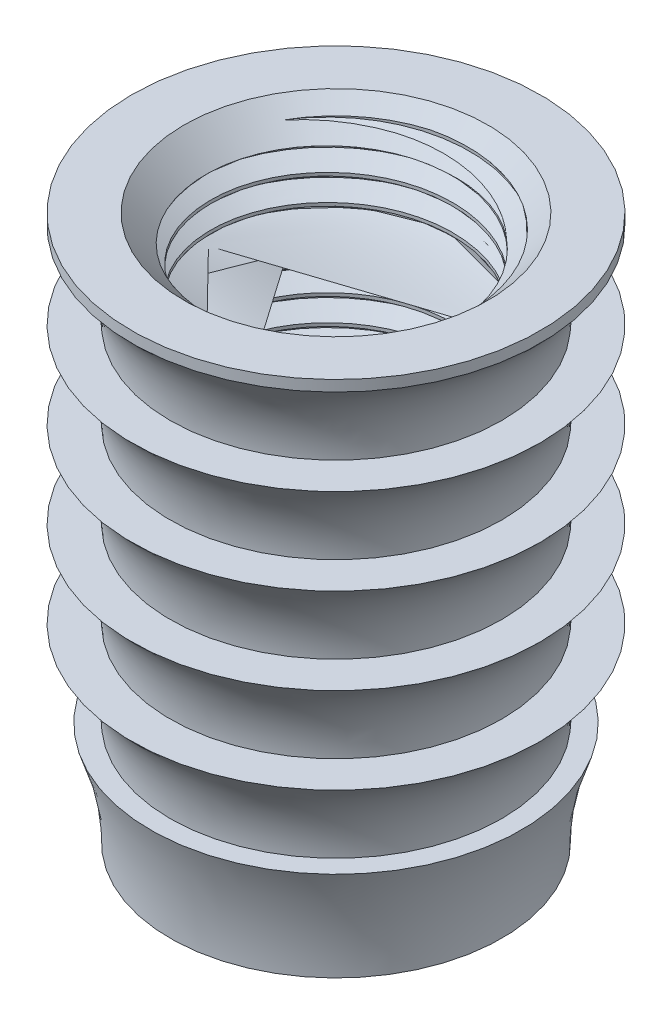
SolidWorks part; units mm, degrees
ref_plane "Front Plane" through (0, 0, 0) normal (0, 0, 1) x (1, 0, 0)
ref_plane "Top Plane" through (0, 0, 0) normal (0, 1, 0) x (1, 0, 0)
ref_plane "Right Plane" through (0, 0, 0) normal (1, 0, 0) x (0, 0, -1)
sketch "Sketch1" plane through (0, 0, 0) normal (0, 0, 1) x (1, 0, 0)
  line L0 (0, -4.7625) -> (0, 4.7625) construction
  line L1 (2.413, 0) -> (-2.413, 0) construction
  line L2 (2.413, 0) -> (2.413, -0.7938) construction
  line L3 (-3.5687, 4.7625) -> (3.5687, 4.7625) construction
  line L4 (-2.8956, -4.7625) -> (2.8956, -4.7625) construction
  line L5 (-3.2385, -0.7938) -> (3.2385, -0.7938) construction
  line L6 (3.5687, 4.7625) -> (155.9687, 4.7625) construction
  line L7 (-3.5687, 4.7625) -> (-8.3947, 4.7625) construction
  point P4 (0, 0)
  point P8 (0, 0)
  point P12 (0, 4.7625)
  point P15 (0, -4.7625)
  point P18 (0, -0.7938)
  dimension "Thread Size" = 4.826
  dimension "Thread Pitch" = 0.7937
  dimension "Installed Length" = 9.525
  dimension "OD" = 7.1374
  dimension "Small Dia" = 5.7912
  dimension "Barb Dia" = 6.477
  dimension "No of Barbs" = 152.4
  dimension "Botom Barb Proportion" = 4.826
sketch "Sketch2" plane through (0, 0, 0) normal (0, 0, 1) x (1, 0, 0)
  line L0 (-3.5687, 4.7625) -> (-3.5687, 4.572)
  line L3 (-2.8956, 3.0671) -> (-2.8956, 4.572) construction
  line L5 (-2.8956, 3.0671) -> (-2.8956, -2.9527)
  line L6 (-2.8956, -2.9527) -> (-3.2385, -2.9527)
  line L7 (-2.8956, -4.7625) -> (2.8956, -4.7625) construction
  line L8 (-3.5687, 4.7625) -> (-2.6543, 4.7625)
  line L9 (-3.5687, 4.7625) -> (3.5687, 4.7625) construction
  line L10 (-2.6543, 4.7625) -> (-2.413, 4.5212)
  line L11 (-2.413, 4.5212) -> (-2.413, -4.5212)
  line L12 (-2.413, -4.5212) -> (-2.6543, -4.7625)
  line L13 (-2.6543, -4.7625) -> (-2.8956, -4.7625)
  line L14 (-2.6543, 4.7625) -> (-2.413, 4.7625) construction
  line L15 (-2.413, 4.7625) -> (-2.413, 4.5212) construction
  line L16 (-2.6543, -4.7625) -> (-2.413, -4.7625) construction
  line L17 (-2.413, -4.7625) -> (-2.413, -4.5212) construction
  line L18 (0, 4.7625) -> (0, -4.7625) construction
  arc A0 (-3.5687, 4.572) -> (-2.8956, 3.0671) centre (-4.9146, 3.0671) cw
  arc A3 (-3.2385, -2.9527) -> (-2.8956, -4.7625) centre (-7.8428, -4.7625) cw
  dimension "D1" = 0.1905
  dimension "D2" = 1.8098
  dimension "D3" = 5.3086
  dimension "D4" = 1.5049
revolve "Revolve1" add sketch "Sketch2" angle 360 about L18
sketch "Sketch10" plane through (0, 0, 0) normal (0, 0, 1) x (1, 0, 0)
  line L1 (-2.8956, 3.0671) -> (-2.8956, 1.5621)
  line L2 (-2.8956, 3.0671) -> (-2.8956, -2.9527) construction
  line L3 (-2.8956, 3.0671) -> (-3.5687, 3.0671)
  line L4 (-2.8956, 3.0671) -> (-2.8956, 4.572) construction
  arc A0 (-3.5687, 3.0671) -> (-2.8956, 1.5621) centre (-4.9146, 1.5621) cw
revolve "Revolve5" add sketch "Sketch10" angle 360 about L0
pattern_linear "LPattern1" count 4 spacing 1.5049 along (0, -1, 0) of "Revolve5"
sketch "Sketch8" plane through (0, 0, 0) normal (0, 1, 0) x (1, 0, 0)
  line L0 (0, 0) -> (0, -2.413) construction
  circle A0 centre (0, 0) radius 2.413 construction
  point P0 (0, -2.413)
sketch "Sketch3" plane through (0, 0, 0) normal (0, 0, 1) x (1, 0, 0)
  line L1 (-2.413, -4.7625) -> (0, -4.7625)
  line L2 (-2.413, -4.7625) -> (-2.413, 4.7625)
  line L3 (-2.413, 4.7625) -> (0, 4.7625)
  line L4 (0, -4.7625) -> (0, 4.7625)
revolve "Revolve2" add sketch "Sketch3" angle 360 about L4
sketch "Sketch4" plane through (0, -4.7625, 0) normal (0, -1, 0) x (1, 0, 0)
  circle A1 centre (0, 0) radius 2.413
  circle A2 centre (0, 0) radius 2.413
  dimension "D1" = 0
curve "Helix/Spiral1" pitch 0.4547 height 10.3187 turns 22.6955
sketch "Sketch5" plane through (0, 0, 0) normal (0, 0, 1) x (1, 0, 0)
  line L0 (2.4614, -4.7346) -> (2.4614, -5.1892) construction
  line L1 (2.4614, -5.1892) -> (2.0676, -4.9619) construction
  line L2 (2.0676, -4.9619) -> (2.4614, -4.7346) construction
  line L3 (2.116, -4.9339) -> (2.116, -4.9898) construction
  line L4 (2.413, -4.7625) -> (2.413, -5.1613) construction
  line L5 (2.413, -4.9619) -> (2.4614, -4.9619) construction
  line L6 (2.0676, -4.9619) -> (2.116, -4.9619) construction
  line L7 (2.4372, -4.9619) -> (2.4372, -5.1753) construction
  line L8 (2.4614, -4.7346) -> (2.4372, -5.1753)
  line L9 (2.4372, -5.1753) -> (2.116, -4.9898)
  line L10 (2.116, -4.9898) -> (2.116, -4.9339)
  line L11 (2.116, -4.9339) -> (2.4614, -4.7346)
  line L12 (-2.8956, -4.7625) -> (2.8956, -4.7625) construction
  dimension "D1" = 0.4547
  dimension "D2" = 0.0559
sweep "Cut-Sweep1" cut profiles "Sketch5" path "Helix/Spiral1" align with end faces yes
sketch "Sketch6" plane through (0, 0, 0) normal (0, 0, 1) x (1, 0, 0)
  line L0 (-2.6543, -4.7625) -> (0, -2.1082)
  line L1 (0, -2.1082) -> (0, -4.7625)
  line L2 (-2.8956, -4.7625) -> (2.8956, -4.7625) construction
  line L3 (0, -4.7625) -> (-2.6543, -4.7625)
  line L4 (-2.413, -4.5212) -> (-2.6543, -4.7625) construction
  line L5 (-2.6543, 4.7625) -> (0, 4.7625) construction
  line L6 (0, 4.7625) -> (0, 2.1082) construction
  line L7 (0, 2.1082) -> (-2.6543, 4.7625) construction
  line L8 (-2.6543, 4.7625) -> (-2.413, 4.5212) construction
revolve "Revolve3" add sketch "Sketch6" angle 360 about L6
sketch "Sketch7" plane through (0, -4.7625, 0) normal (0, -1, 0) x (1, 0, 0)
  circle A0 centre (0, 0) radius 2.6543 construction
  circle A1 centre (0, 0) radius 2.6543
sketch "Sketch9" plane through (0, 0, 0) normal (0, 0, 1) x (1, 0, 0)
  line L0 (0, 4.7625) -> (0, 2.1082) construction
  line L1 (-2.6543, 4.7625) -> (0, 4.7625) construction
  line L2 (0, 2.1082) -> (-2.6543, 4.7625) construction
  line L3 (0, 4.7625) -> (0, 2.1082)
  line L4 (-2.6543, 4.7625) -> (0, 4.7625)
  line L5 (0, 2.1082) -> (-2.6543, 4.7625)
revolve "Revolve4" add sketch "Sketch9" angle 360 about L3
extrude "Boss-Extrude1" add sketch "Sketch7" against normal up to surface (9.525 mm away) up to face at (-3.5687, 4.7625, 0)
combine bodies "Combine1" operation type subtract main body 108 bodies to subtract 110
equation "\"D1@Sketch2\"=\"Installed Length@Sketch1\"*.02"
equation "\"D2@Sketch2\"=\"Installed Length@Sketch1\"*\"Botom Barb Proportion@Sketch1\""
equation "\"D3@Sketch2\"=\"Thread Size@Sketch1\"*1.1"
equation "\"D3@Helix/Spiral1\"=\"Installed Length@sketch1\"+\"Thread Pitch@sketch1\""
equation "\"D4@Sketch2\" =  ( \"Installed Length@Sketch1\" *  ( .98 - \"Botom Barb Proportion@Sketch1\" )  )  /  ( \"No of Barbs@Sketch1\" - 1 ) "
equation "\"D1@LPattern1\"=\"No of Barbs@Sketch1\"-2"
equation "\"D3@LPattern1\"=( \"Installed Length@Sketch1\" *  ( .98 - \"Botom Barb Proportion@Sketch1\" )  )  /  ( \"No of Barbs@Sketch1\" - 1 )"
